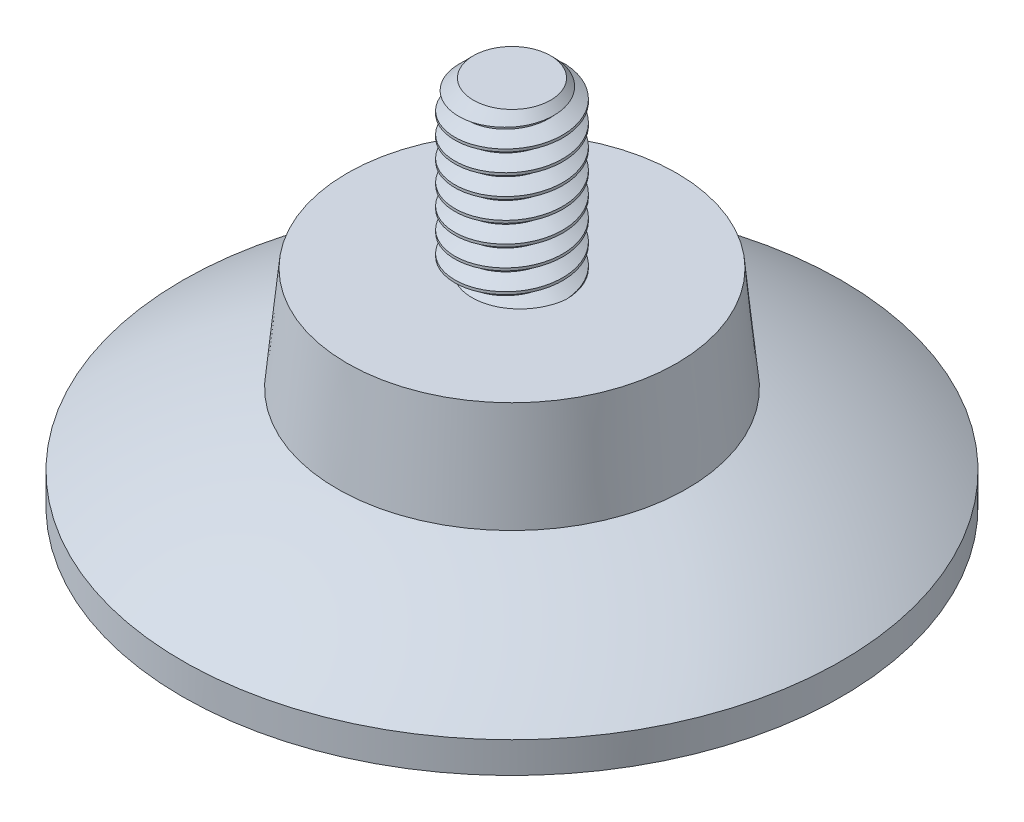
SolidWorks part; units mm, degrees
ref_plane "Front" through (0, 0, 0) normal (0, 0, 1) x (1, 0, 0)
ref_plane "Top" through (0, 0, 0) normal (0, 1, 0) x (1, 0, 0)
ref_plane "Right" through (0, 0, 0) normal (1, 0, 0) x (0, 0, -1)
sketch "Sketch1" plane through (0, 0, 0) normal (0, 0, 1) x (1, 0, 0)
  line L0 (-12.7, 0) -> (12.7, 0) construction
  line L1 (0, 0) -> (0, 14.3002) construction
  line L2 (12.7, 0) -> (12.7, 1.1938) construction
  line L3 (6.35, 7.9502) -> (6.7437, 3.9624) construction
  line L4 (6.35, 7.9502) -> (-6.35, 7.9502) construction
  line L5 (-6.35, 7.9502) -> (-6.7437, 3.9624) construction
  line L6 (-12.7, 0) -> (-12.7, 1.1938) construction
  line L7 (-2.0828, 14.3002) -> (2.0828, 14.3002) construction
  line L8 (2.0828, 14.3002) -> (2.0828, 7.9502)
  line L9 (-2.0828, 14.3002) -> (-2.0828, 7.9502) construction
  line L10 (-6.7437, 3.9624) -> (6.7437, 3.9624) construction
  line L11 (11.5062, 0) -> (12.7, 0) construction
  line L12 (2.0828, 7.9502) -> (0, 7.9502)
  line L13 (0, 7.9502) -> (0, 14.3002)
  line L14 (0, 14.3002) -> (2.0828, 14.3002)
  arc A0 (-11.5062, 0) -> (11.5062, 0) centre (0, -18.3373) cw construction
  arc A1 (12.7, 1.1938) -> (6.7437, 3.9624) centre (0, -18.3373) ccw construction
  arc A2 (-12.7, 1.1938) -> (-6.7437, 3.9624) centre (0, -18.3373) cw construction
  point P7 (0, 7.9502)
  point P11 (0, 3.311)
  point P18 (0, 14.3002)
  point P19 (0, 3.9624)
revolve "Revolve1" add sketch "Sketch1" angle 360 mid plane about L13
sketch "Sketch2" plane through (0, 14.3002, 0) normal (0, 1, 0) x (1, 0, 0)
  circle A1 centre (0, 0) radius 2.0828
  circle A2 centre (0, 0) radius 2.0828
  dimension "D1" = 0
curve "Helix/Spiral1" pitch 0.7937 height 7.1437 turns 9 parameters "Thread Pitch"=0.7937
chamfer "Chamfer1" distance 0.5953 angle 45 1 edges at (0, 14.3002, -2.0828)
sketch "Sketch4" plane through (0, 0, 0) normal (0, 0, 1) x (1, 0, 0)
  line L0 (2.0828, 14.3002) -> (2.0828, 14.9947) construction
  line L1 (2.0828, 14.9947) -> (1.5672, 14.6971) construction
  line L2 (1.5672, 14.6971) -> (1.5672, 14.5979)
  line L3 (1.5672, 14.5979) -> (2.0828, 14.3002) construction
  line L4 (1.5672, 14.6475) -> (2.0828, 14.6475) construction
  line L5 (1.825, 14.449) -> (1.825, 14.8459) construction
  line L6 (1.5672, 14.6971) -> (2.1082, 15.0094)
  line L7 (1.5672, 14.5979) -> (2.1082, 14.2855)
  line L8 (2.1082, 14.2855) -> (2.1082, 15.0094)
  dimension "D1" = 0.0992
  dimension "D2" = 0.3969
  dimension "D3" = 0.0254
  dimension "D4" = 60
sweep "Cut-Sweep1" cut profiles "Sketch4" path "Helix/Spiral1"
sketch "Sketch5" plane through (0, 0, 0) normal (0, 0, 1) x (1, 0, 0)
  line L0 (0, 7.9502) -> (6.35, 7.9502)
  line L1 (6.35, 7.9502) -> (6.7437, 3.9624) construction
  line L2 (6.35, 7.9502) -> (6.7437, 3.9624)
  line L3 (12.7, 0) -> (12.7, 1.1938) construction
  line L4 (12.7, 0) -> (12.7, 1.1938)
  line L5 (11.5062, 0) -> (12.7, 0)
  line L6 (0, 3.311) -> (0, 7.9502)
  arc A0 (12.7, 1.1938) -> (6.7437, 3.9624) centre (0, -18.3373) ccw construction
  arc A1 (11.5062, 0) -> (-11.5062, 0) centre (0, -18.3373) ccw construction
  arc A2 (12.7, 1.1938) -> (6.7437, 3.9624) centre (0, -18.3373) ccw
  arc A3 (11.5062, 0) -> (0, 3.311) centre (0, -18.3373) ccw
revolve "Revolve2" add sketch "Sketch5" angle 360 mid plane about L1
equation "\"D3@Helix/Spiral1\" = \"Thread Lg@Sketch1\" + \"Thread Pitch@Helix/Spiral1\""
equation "\"D1@Chamfer1\" = \"Thread Pitch@Helix/Spiral1\" * .75"
equation "\"D1@Sketch4\" = \"Thread Pitch@Helix/Spiral1\" * .125"
equation "\"D2@Sketch4\" = \"Thread Pitch@Helix/Spiral1\" * .5"
